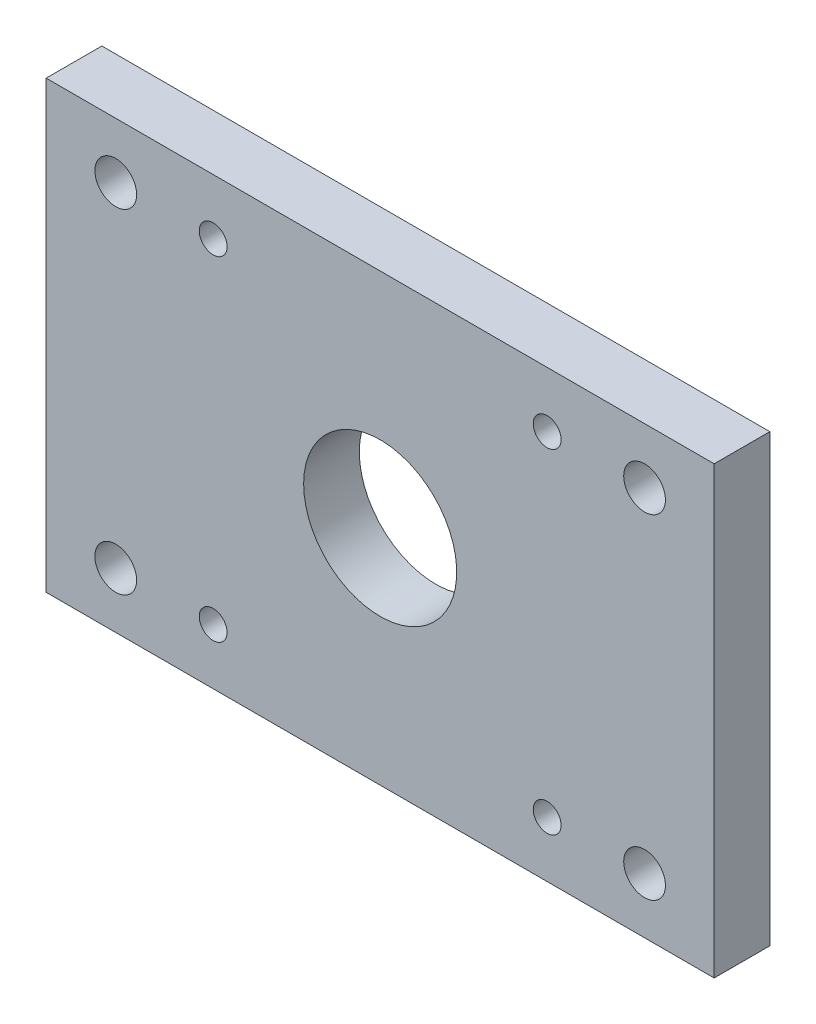
SolidWorks part; units mm, degrees
material "Perspex (TM) GS Acrylic Cast Sheet"
ref_plane "Front Plane" through (0, 0, 0) normal (0, 0, 1) x (1, 0, 0)
ref_plane "Top Plane" through (0, 0, 0) normal (0, 1, 0) x (1, 0, 0)
ref_plane "Right Plane" through (0, 0, 0) normal (1, 0, 0) x (0, 0, -1)
sketch "Sketch1" plane through (0, 0, 0) normal (0, 0, 1) x (1, 0, 0)
  line L1 (0, 0) -> (76.2, 0)
  line L2 (0, 0) -> (0, 50.8)
  line L3 (0, 50.8) -> (76.2, 50.8)
  line L4 (76.2, 0) -> (76.2, 50.8)
  dimension "D1" = 50.8
  dimension "D2" = 76.2
extrude "Boss-Extrude1" add sketch "Sketch1" along normal blind 6.35
sketch "Sketch2" plane through (0, 0, 0) normal (0, 0, -1) x (-1, 0, 0)
  line L0 (0, 25.4) -> (-76.2, 25.4) construction
  line L1 (0, 50.8) -> (0, 0) construction
  line L2 (-76.2, 0) -> (-76.2, 50.8) construction
  line L3 (-38.1, 50.8) -> (-38.1, 0) construction
  line L4 (-76.2, 50.8) -> (0, 50.8) construction
  line L5 (0, 0) -> (-76.2, 0) construction
  circle A0 centre (-38.1, 25.4) radius 8.7313
  dimension "D1" = 17.4625
sketch "Sketch3" plane through (0, 0, 0) normal (0, 0, -1) x (-1, 0, 0)
  line L0 (-76.2, 0) -> (-76.2, 50.8) construction
  line L1 (-76.2, 50.8) -> (0, 50.8) construction
  circle A0 centre (-68.2625, 44.45) radius 2.3813
  dimension "D1" = 4.7625
  dimension "D2" = 7.9375
  dimension "D3" = 6.35
extrude "Cut-Extrude6" cut sketch "Sketch3" against normal through all
sketch "Sketch4" plane through (0, 0, 0) normal (0, 0, -1) x (-1, 0, 0)
  line L0 (-38.1, 50.8) -> (-38.1, 0) construction
  line L1 (-76.2, 50.8) -> (0, 50.8) construction
  line L2 (0, 0) -> (-76.2, 0) construction
  line L3 (-76.2, 25.4) -> (0, 25.4) construction
  line L4 (-76.2, 0) -> (-76.2, 50.8) construction
  line L5 (0, 50.8) -> (0, 0) construction
ref_plane "Plane1" through (38.1, 0, 0) normal (1, 0, 0) x (0, -1, 0)
mirror "Mirror1" about plane through (38.1, 0, 0) normal (1, 0, 0) of "Cut-Extrude6"
ref_plane "Plane2" through (0, 25.4, 0) normal (0, -1, 0) x (-1, 0, 0)
mirror "Mirror2" about plane through (0, 25.4, 0) normal (0, -1, 0) of "Mirror1"
extrude "Cut-Extrude7" cut sketch "Sketch2" against normal through all contours A0
sketch "Sketch5" plane through (0, 0, 0) normal (0, 0, -1) x (-1, 0, 0)
  circle A0 centre (-19.05, 44.45) radius 1.5875
  circle A1 centre (-19.05, 6.35) radius 1.5875
  circle A2 centre (-57.15, 44.45) radius 1.5875
  circle A3 centre (-57.15, 6.35) radius 1.5875
  dimension "D1" = 3.175
  dimension "D2" = 3.175
  dimension "D3" = 3.175
  dimension "D4" = 3.175
extrude "Cut-Extrude8" cut sketch "Sketch5" against normal through all
equation "\"dist\"= 10"
